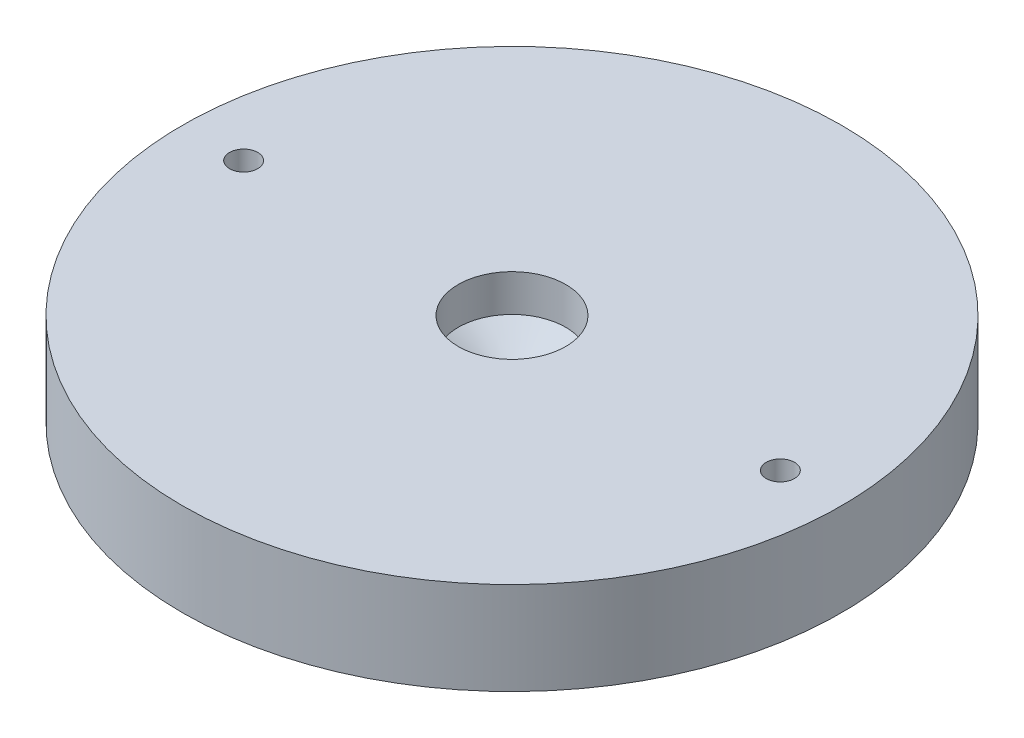
SolidWorks part; units mm, degrees
ref_plane "Front Plane" through (0, 0, 0) normal (0, 0, 1) x (1, 0, 0)
ref_plane "Top Plane" through (0, 0, 0) normal (0, 1, 0) x (1, 0, 0)
ref_plane "Right Plane" through (0, 0, 0) normal (1, 0, 0) x (0, 0, -1)
sketch "Sketch1" plane through (0, 0, 0) normal (0, 1, 0) x (1, 0, 0)
  line L0 (0, 0) -> (-14.478, 0) construction
  line L1 (0, 0) -> (14.478, 0) construction
  circle A0 centre (0, 0) radius 17.78
  circle A1 centre (-14.478, 0) radius 0.762
  circle A2 centre (14.478, 0) radius 0.762
  point P6 (0, 0)
  dimension "D1" = 35.56
  dimension "D2" = 1.524
  dimension "D3" = 1.524
  dimension "D4" = 28.956
extrude "Boss-Extrude1" add sketch "Sketch1" along normal blind 5
sketch "Sketch5" plane through (0, 0, 0) normal (0, -1, 0) x (1, 0, 0)
  circle A0 centre (0, 13.97) radius 2.032
  point P2 (0, 0)
  point P4 (0, 12.1584)
  dimension "D1" = 4.064
  dimension "D2" = 13.97
extrude "Cut-Extrude1" cut sketch "Sketch5" against normal blind 3
hole_wizard "M5 Clearance Hole2" positions "Sketch8" profile "Sketch9" hole size "M5" standard "ANSI Metric"
sketch "Sketch8" plane through (0, 5, 0) normal (0, 1, 0) x (1, 0, 0)
  point P0 (0, 0)
sketch "Sketch9" plane through (0, 5, 0) normal (1, 0, 0) x (0, 0, 1)
  line L0 (0, 0) -> (0, 3.7425)
  line L1 (0, 3.7425) -> (2.9, 2)
  line L2 (2.9, 2) -> (2.9, 0)
  line L5 (2.9, 0) -> (0, 0)
  line L10 (0, 3.7425) -> (-2.9, 2) construction
  line L11 (0, -6.35) -> (0, 107.95) construction
  dimension "Hole Dia." = 5.8
  dimension "Hole Depth" = 2
  dimension "Drill Angle" = 118
equation "\"press fit\"= 0.25mm"
equation "\"servo hole size\" = 0.0472in + \"press fit\""
equation "\"D2@Sketch1\"=\"servo hole size\""
equation "\"D3@Sketch1\"=\"servo hole size\""
equation "\"hole distance\"= 28.9mm"
equation "\"D4@Sketch1\"=\"hole distance\""
equation "\"pin diamiter\"= 0.15in"
equation "\"D1@Sketch5\"=\"pin diamiter\"+\"press fit\""
equation "\"middle hole\" = 0.2in"
